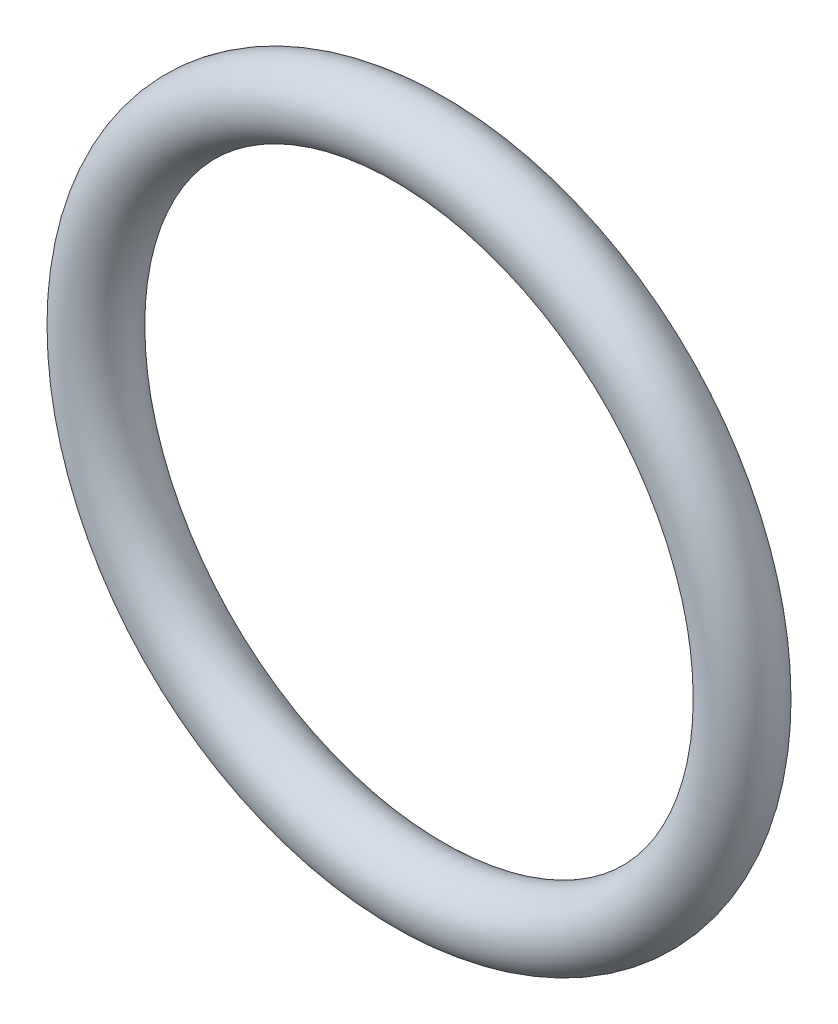
SolidWorks part; units mm, degrees
ref_plane "Front Plane" through (0, 0, 0) normal (0, 0, 1) x (1, 0, 0)
ref_plane "Top Plane" through (0, 0, 0) normal (0, 1, 0) x (1, 0, 0)
ref_plane "Right Plane" through (0, 0, 0) normal (1, 0, 0) x (0, 0, -1)
ref_plane "Plane1" through (0, 0, 0) normal (1, 0, 0) x (0, 0, -1)
sketch "Sketch1" plane through (0, 0, 0) normal (1, 0, 0) x (0, 0, -1)
  line L0 (0.7493, 0) -> (-0.7493, 0) construction
  circle A0 centre (0, 6.9977) radius 0.7493
revolve "Revolve1" add sketch "Sketch1" angle 360 about L0 reverse direction yes
